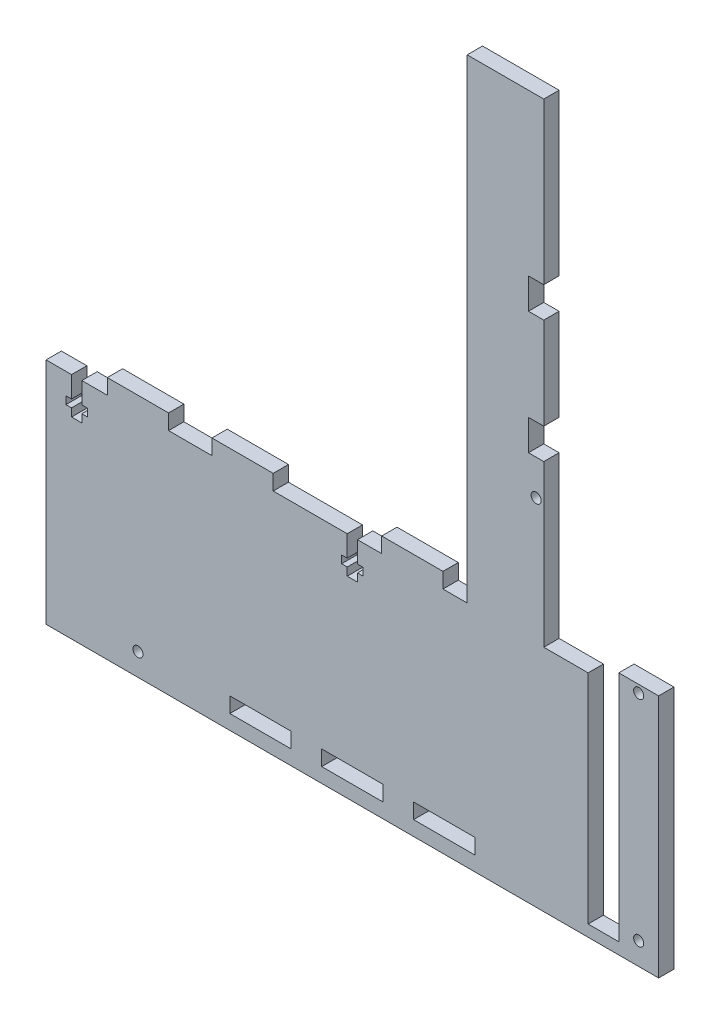
SolidWorks part; units mm, degrees
ref_plane "Front Plane" through (0, 0, 0) normal (0, 0, 1) x (1, 0, 0)
ref_plane "Top Plane" through (0, 0, 0) normal (0, 1, 0) x (1, 0, 0)
ref_plane "Right Plane" through (0, 0, 0) normal (1, 0, 0) x (0, 0, -1)
sketch "Sketch1" plane through (0, 0, 0) normal (0, 1, 0) x (1, 0, 0)
  line L0 (0, 15.4483) -> (0, 24.666) construction
  line L1 (-143.9938, 3.175) -> (110.0062, 3.175)
  line L2 (-143.9938, 3.175) -> (-143.9938, -3.175)
  line L3 (-143.9938, -3.175) -> (110.0062, -3.175)
  line L4 (110.0062, 3.175) -> (110.0062, -3.175)
  line L5 (8.1935, 0) -> (24.922, 0) construction
  dimension "D2" = 6.35
extrude "Base Extrusion" add sketch "Sketch1" along normal up to surface (94.9689 mm away)
sketch "Sketch4" plane through (0, 0, 3.175) normal (0, 0, 1) x (1, 0, 0)
  line L0 (110.0062, 12.4189) -> (90.9928, 12.4189) construction
  line L1 (-67.7938, 12.4189) -> (-42.3938, 12.4189)
  line L2 (-67.7938, 12.4189) -> (-67.7938, 6.0689)
  line L3 (-67.7938, 6.0689) -> (-42.3938, 6.0689)
  line L4 (-42.3938, 12.4189) -> (-42.3938, 6.0689)
  line L5 (-29.6938, 12.4189) -> (-4.2938, 12.4189)
  line L6 (-29.6938, 12.4189) -> (-29.6938, 6.0689)
  line L7 (-29.6938, 6.0689) -> (-4.2938, 6.0689)
  line L8 (-4.2938, 12.4189) -> (-4.2938, 6.0689)
  line L9 (8.4062, 12.4189) -> (33.8062, 12.4189)
  line L10 (8.4062, 12.4189) -> (8.4062, 6.0689)
  line L11 (8.4062, 6.0689) -> (33.8062, 6.0689)
  line L12 (33.8062, 12.4189) -> (33.8062, 6.0689)
  line L13 (110.0062, 6.0689) -> (90.9928, 6.0689) construction
  line L14 (110.0062, 12.4189) -> (90.9928, 12.4189) construction
  line L15 (110.0062, 6.0689) -> (90.9928, 6.0689) construction
  line L17 (-16.9938, 40.6411) -> (-16.9938, -10.2729) construction
  line L18 (-143.9938, 94.9689) -> (-143.9938, 0) construction
  line L19 (110.0062, 94.9689) -> (110.0062, 0) construction
  dimension "D1" = 25.4
  dimension "D2" = 25.4
  dimension "D3" = 25.4
  dimension "D5" = 12.7
  dimension "D6" = 12.7
extrude "Tab Holes to Chassis Base" cut sketch "Sketch4" against normal through all
sketch "Sketch5" plane through (0, 0, 3.175) normal (0, 0, 1) x (1, 0, 0)
  line L0 (-16.9938, 67.1576) -> (-16.9938, 113.4981) construction
  line L1 (-143.9938, 94.9689) -> (-143.9938, 0) construction
  line L2 (110.0062, 94.9689) -> (110.0062, 0) construction
  line L3 (110.0062, 94.9689) -> (-143.9938, 94.9689) construction
  line B0 (-14.8602, 94.9689) -> (-19.1274, 94.9689)
  line B1 (-19.1274, 83.0309) -> (-21.4388, 83.0309)
  line B2 (-21.4388, 83.0309) -> (-21.4388, 86.2059)
  line B3 (-21.4388, 86.2059) -> (-19.1274, 86.2059)
  line B4 (-19.1274, 86.2059) -> (-19.1274, 94.9689)
  line B5 (-19.1274, 83.0309) -> (-19.1274, 79.7289)
  line B6 (-19.1274, 79.7289) -> (-14.8602, 79.7289)
  line B7 (-14.8602, 83.0309) -> (-14.8602, 79.7289)
  line B8 (-14.8602, 86.2059) -> (-14.8602, 94.9689)
  line B9 (-12.5488, 86.2059) -> (-14.8602, 86.2059)
  line B10 (-12.5488, 83.0309) -> (-12.5488, 86.2059)
  line B11 (-14.8602, 83.0309) -> (-12.5488, 83.0309)
sketch_block_instance "TSlot-1"
sketch_block "TSlot" parameters "D1"=3.302, "D2"=3.175
extrude "T Slot Center" cut sketch "Sketch5" against normal through all
sketch "Sketch6" plane through (0, 0, 3.175) normal (0, 0, 1) x (1, 0, 0)
  line L0 (110.0062, 94.9689) -> (-14.8602, 94.9689) construction
  line L1 (62.3812, 94.9689) -> (30.6312, 94.9689)
  line L2 (62.3812, 94.9689) -> (62.3812, 291.8189)
  line L3 (62.3812, 291.8189) -> (30.6312, 291.8189)
  line L4 (30.6312, 94.9689) -> (30.6312, 291.8189)
  line L5 (62.3812, 12.4189) -> (62.3812, 144.9053) construction
  line L6 (56.0312, 291.8189) -> (62.3812, 291.8189) construction
  dimension "D1" = 31.75
extrude "Arm Support" add sketch "Sketch6" against normal up to surface (6.35 mm away) up to face at (-16.9938, 76.0175, -3.175)
sketch "Sketch8" plane through (0, 94.9689, 0) normal (0, 1, 0) x (1, 0, 0)
  line L0 (80.775, -3.175) -> (80.775, 3.175)
  line L1 (80.775, -3.175) -> (93.475, -3.175)
  line L2 (80.775, 3.175) -> (93.475, 3.175)
  line L3 (93.475, -3.175) -> (93.475, 3.175)
  line L4 (110.0062, -3.175) -> (62.3812, -3.175) construction
  line L5 (62.3812, 3.175) -> (110.0062, 3.175) construction
  line L6 (87.125, -7.9885) -> (87.125, 24.6597) construction
extrude "Arm Clearance" cut sketch "Sketch8" against normal offset from surface (90.2064 mm away) 4.7625 up to face at (-16.9938, 0, 0)
sketch "Sketch9" plane through (0, 0, 3.175) normal (0, 0, 1) x (1, 0, 0)
  line L0 (96.3524, 9.2439) -> (106.7258, 9.2439) construction
  line L3 (101.7406, 25.5557) -> (101.7406, 3.267) construction
  line L4 (93.475, 4.7625) -> (93.475, 94.9689) construction
  line L5 (110.0062, 94.9689) -> (110.0062, 0) construction
  circle A0 centre (101.7406, 9.2439) radius 2.0955
  dimension "D1" = 4.191
extrude "Base Mounting Hole 1" cut sketch "Sketch9" against normal through all
sketch "Sketch10" plane through (0, 0, 3.175) normal (0, 0, 1) x (1, 0, 0)
  line L0 (-78.6997, 9.2439) -> (-124.1873, 9.2439) construction
  line L5 (-42.3938, 12.4189) -> (-67.7938, 12.4189) construction
  line L6 (-67.7938, 6.0689) -> (-42.3938, 6.0689) construction
  line L7 (-105.8938, 38.7875) -> (-105.8938, -6.1881) construction
  line L8 (-143.9938, 94.9689) -> (-143.9938, 0) construction
  line L9 (-67.7938, 12.4189) -> (-67.7938, 6.0689) construction
  circle A0 centre (-105.8938, 9.2439) radius 2.0955
  circle A1 centre (101.7406, 9.2439) radius 2.0955 construction
extrude "Base Mounting Hole 2" cut sketch "Sketch10" against normal through all
sketch "Sketch11" plane through (0, 0, 3.175) normal (0, 0, 1) x (1, 0, 0)
  line L0 (39.2564, 147.0389) -> (78.7704, 147.0389) construction
  line L1 (62.3812, 149.1725) -> (56.0312, 149.1725) construction
  line L2 (56.0312, 144.9053) -> (62.3812, 144.9053) construction
  line L3 (59.2062, 189.1979) -> (59.2062, 134.4872) construction
  line L4 (62.3812, 291.8189) -> (62.3812, 94.9689) construction
  line L5 (56.0312, 149.1725) -> (56.0312, 161.6439) construction
  circle A0 centre (59.2062, 147.0389) radius 2.0955
  circle A1 centre (101.7406, 9.2439) radius 2.0955 construction
extrude "Arm Support Mounting Hole" cut sketch "Sketch11" against normal through all
sketch "Sketch12" plane through (0, 0, 3.175) normal (0, 0, 1) x (1, 0, 0)
  line L0 (62.3812, 94.9689) -> (62.3812, 291.8189) construction
  line L1 (56.0312, 225.1439) -> (62.3812, 225.1439)
  line L2 (56.0312, 225.1439) -> (56.0312, 212.4439)
  line L3 (56.0312, 212.4439) -> (62.3812, 212.4439)
  line L4 (62.3812, 225.1439) -> (62.3812, 212.4439)
  line L5 (56.0312, 174.3439) -> (62.3812, 174.3439)
  line L6 (56.0312, 174.3439) -> (56.0312, 161.6439)
  line L7 (56.0312, 161.6439) -> (62.3812, 161.6439)
  line L8 (62.3812, 174.3439) -> (62.3812, 161.6439)
  line L9 (56.0312, 161.6439) -> (56.0312, 174.3439) construction
  line L10 (56.0312, 174.3439) -> (62.3812, 174.3439) construction
  line L11 (62.3812, 161.6439) -> (56.0312, 161.6439) construction
  line L12 (56.0312, 212.4439) -> (56.0312, 225.1439) construction
  line L13 (56.0312, 225.1439) -> (62.3812, 225.1439) construction
  line L14 (62.3812, 212.4439) -> (56.0312, 212.4439) construction
extrude "Arm Support Tab Slots" cut sketch "Sketch12" against normal through all
sketch "Sketch13" plane through (0, 94.9689, 0) normal (0, 1, 0) x (1, 0, 0)
  line L0 (-143.9938, 3.175) -> (-19.1274, 3.175) construction
  line L1 (93.475, 3.175) -> (110.0062, 3.175)
  line L2 (93.475, 3.175) -> (93.475, -3.175)
  line L3 (93.475, -3.175) -> (110.0062, -3.175)
  line L4 (110.0062, 3.175) -> (110.0062, -3.175)
  line L5 (-118.5938, 3.175) -> (-93.1938, 3.175)
  line L6 (-118.5938, 3.175) -> (-118.5938, -3.175)
  line L7 (-118.5938, -3.175) -> (-93.1938, -3.175)
  line L8 (-93.1938, 3.175) -> (-93.1938, -3.175)
  line L9 (-19.1274, -3.175) -> (-143.9938, -3.175) construction
  line L10 (-14.8602, 3.175) -> (30.6312, 3.175) construction
  line L11 (-4.8145, 3.175) -> (20.5855, 3.175)
  line L12 (-4.8145, 3.175) -> (-4.8145, -3.175)
  line L13 (-4.8145, -3.175) -> (20.5855, -3.175)
  line L14 (20.5855, 3.175) -> (20.5855, -3.175)
  line L15 (30.6312, -3.175) -> (-14.8602, -3.175) construction
  line L16 (7.8855, 19.4293) -> (7.8855, -15.2554) construction
  line L17 (-75.2106, 3.175) -> (-49.8106, 3.175)
  line L18 (-75.2106, 3.175) -> (-75.2106, -3.175)
  line L19 (-75.2106, -3.175) -> (-49.8106, -3.175)
  line L20 (-49.8106, 3.175) -> (-49.8106, -3.175)
  line L21 (-14.8602, 3.175) -> (-14.8602, -3.175) construction
  line L22 (30.6312, 3.175) -> (30.6312, -3.175) construction
  line L23 (-105.8938, 22.3632) -> (-105.8938, -15.2554) construction
  line L28 (-62.5106, 22.3632) -> (-62.5106, -21.1411) construction
  line L29 (-19.1274, 3.175) -> (-19.1274, -3.175) construction
  dimension "D1" = 25.4
extrude "Top Plate Tab" add sketch "Sketch13" along normal blind 6.35
sketch "Sketch14" plane through (0, 0, 3.175) normal (0, 0, 1) x (1, 0, 0)
  line L0 (-131.2938, 71.8951) -> (-131.2938, 106.4008) construction
  line L1 (-118.5938, 94.9689) -> (-143.9938, 94.9689) construction
  line L2 (-143.9938, 94.9689) -> (-143.9938, 0) construction
  line L3 (-118.5938, 101.3189) -> (-118.5938, 94.9689) construction
  line B0 (-129.1602, 94.9689) -> (-133.4274, 94.9689)
  line B1 (-133.4274, 83.0309) -> (-135.7388, 83.0309)
  line B2 (-135.7388, 83.0309) -> (-135.7388, 86.2059)
  line B3 (-135.7388, 86.2059) -> (-133.4274, 86.2059)
  line B4 (-133.4274, 86.2059) -> (-133.4274, 94.9689)
  line B5 (-133.4274, 83.0309) -> (-133.4274, 79.7289)
  line B6 (-133.4274, 79.7289) -> (-129.1602, 79.7289)
  line B7 (-129.1602, 83.0309) -> (-129.1602, 79.7289)
  line B8 (-129.1602, 86.2059) -> (-129.1602, 94.9689)
  line B9 (-126.8488, 86.2059) -> (-129.1602, 86.2059)
  line B10 (-126.8488, 83.0309) -> (-126.8488, 86.2059)
  line B11 (-129.1602, 83.0309) -> (-126.8488, 83.0309)
sketch_block_instance "TSlot-3"
extrude "T Slot Top Corner" cut sketch "Sketch14" against normal through all
sketch "Sketch15" plane through (0, 0, 3.175) normal (0, 0, 1) x (1, 0, 0)
  line L0 (101.7406, 99.797) -> (101.7406, 89.693) construction
  line L1 (93.475, 4.7625) -> (93.475, 101.3189) construction
  line L2 (110.0062, 101.3189) -> (110.0062, 0) construction
  line L3 (95.644, 98.1439) -> (106.8624, 98.1439) construction
  line L7 (62.3812, 94.9689) -> (80.775, 94.9689) construction
  line L8 (-4.8145, 101.3189) -> (20.5855, 101.3189) construction
  circle A0 centre (101.7406, 98.1439) radius 2.0955
  dimension "D1" = 4.191
extrude "Cut-Extrude8" cut sketch "Sketch15" against normal through all
